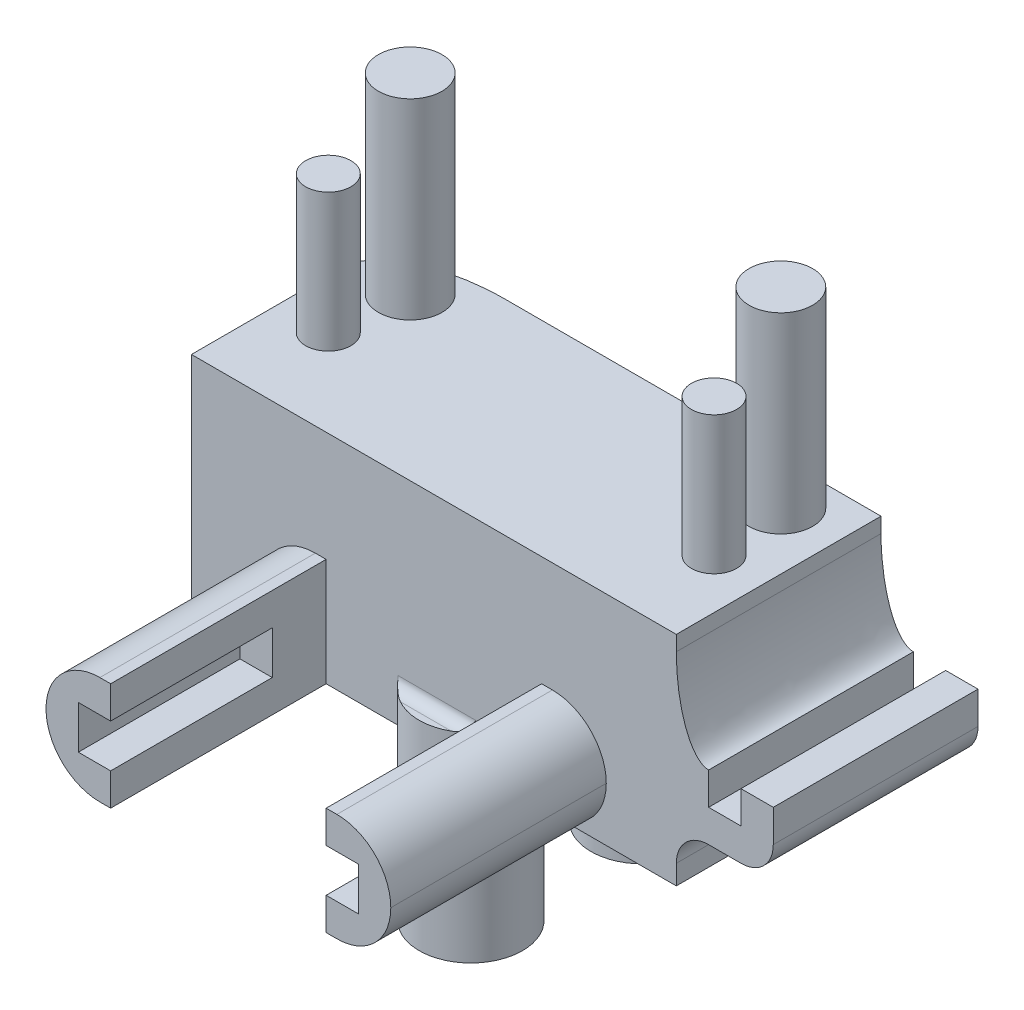
SolidWorks part; units mm, degrees
ref_plane "Front Plane" through (0, 0, 0) normal (0, 0, 1) x (1, 0, 0)
ref_plane "Top Plane" through (0, 0, 0) normal (0, 1, 0) x (1, 0, 0)
ref_plane "Right Plane" through (0, 0, 0) normal (1, 0, 0) x (0, 0, -1)
sketch "Sketch1" plane through (0, 0, 0) normal (0, 1, 0) x (1, 0, 0)
  line L1 (-40.1858, -24.5795) -> (-17.6858, -24.5795)
  line L2 (-40.1858, -24.5795) -> (-40.1858, -17.5795)
  line L3 (-40.1858, -17.5795) -> (-17.6858, -17.5795)
  line L4 (-17.6858, -24.5795) -> (-17.6858, -17.5795)
  dimension "D1" = 22.5
  dimension "D2" = 7
extrude "Boss-Extrude1" add sketch "Sketch1" along normal blind 1.5
sketch "Sketch2" plane through (0, 1.5, 0) normal (0, 1, 0) x (1, 0, 0)
  line L0 (-17.6858, -24.5795) -> (-17.6858, -17.5795) construction
  line L2 (-40.1858, -24.5795) -> (-17.6858, -24.5795) construction
  circle A0 centre (-37.5358, -19.5795) radius 1.475
  circle A1 centre (-20.3358, -19.5795) radius 1.475
  dimension "D1" = 2.95
  dimension "D2" = 2.95
  dimension "D3" = 17.2
  dimension "D4" = 2.65
  dimension "D5" = 5
  dimension "D6" = 5
extrude "Boss-Extrude2" add sketch "Sketch2" along normal blind 11.5
sketch "Sketch3" plane through (0, 1.5, 0) normal (0, 1, 0) x (1, 0, 0)
  circle A0 centre (-37.8858, -23.0295) radius 1.05
  circle A1 centre (-19.9858, -23.0295) radius 1.05
  circle A2 centre (-37.5358, -19.5795) radius 1.475 construction
  circle A3 centre (-20.3358, -19.5795) radius 1.475 construction
  dimension "D1" = 2.1
  dimension "D2" = 2.1
  dimension "D3" = 0.35
  dimension "D4" = 0.35
  dimension "D5" = 3.45
  dimension "D6" = 3.45
extrude "Boss-Extrude3" add sketch "Sketch3" along normal blind 9
sketch "Sketch4" plane through (0, 0, 0) normal (0, -1, 0) x (-1, 0, 0)
  line L0 (40.1858, -17.5795) -> (40.1858, -24.5795) construction
  line L1 (17.6858, -24.5795) -> (40.1858, -24.5795)
  line L2 (17.6858, -24.5795) -> (17.6858, -27.0795)
  line L3 (17.6858, -27.0795) -> (40.1858, -27.0795)
  line L4 (40.1858, -24.5795) -> (40.1858, -27.0795)
  line L6 (20.9358, -27.0795) -> (23.9358, -27.0795)
  line L7 (20.9358, -27.0795) -> (20.9358, -29.9823)
  line L8 (20.9358, -29.9823) -> (23.9358, -29.9823)
  line L9 (23.9358, -27.0795) -> (23.9358, -29.9823)
  line L10 (32.4358, -27.0795) -> (35.4358, -27.0795)
  line L11 (32.4358, -27.0795) -> (32.4358, -28.8632)
  line L12 (32.4358, -28.8632) -> (35.4358, -28.8632)
  line L13 (35.4358, -27.0795) -> (35.4358, -28.8632)
  line M13 (40.1858, -24.5795) -> (40.1858, -17.5795)
  line M14 (40.1858, -17.5795) -> (17.6858, -17.5795)
  line M15 (17.6858, -17.5795) -> (17.6858, -24.5795)
  line M16 (17.6858, -24.5795) -> (40.1858, -24.5795)
  dimension "D1" = 0
  dimension "D2" = 3.25
  dimension "D3" = 4.75
  dimension "D4" = 2.5
  dimension "D5" = 3
  dimension "D6" = 3
extrude "Boss-Extrude4" add sketch "Sketch4" along normal blind 6 and the other way blind 1.5 contours L4 L2 L3 M16 | M16 M13 M14 M15
sketch "Sketch8" plane through (0, 1.5, 0) normal (0, 1, 0) x (1, 0, 0)
  line L1 (-40.1858, -17.5795) -> (-17.6858, -17.5795)
  line L2 (-40.1858, -17.5795) -> (-40.1858, -27.0795)
  line L3 (-40.1858, -27.0795) -> (-17.6858, -27.0795)
  line L4 (-17.6858, -17.5795) -> (-17.6858, -27.0795)
extrude "Boss-Extrude7" add sketch "Sketch8" along normal blind 2.61
sketch "Sketch9" plane through (0, -6, 0) normal (0, -1, 0) x (-1, 0, 0)
  line L0 (17.6858, -17.5795) -> (17.6858, -27.0795) construction
  line L3 (17.6858, -27.0795) -> (40.1858, -27.0795) construction
  circle A0 centre (28.8108, -25.4895) radius 2.4
  circle A1 centre (28.8108, -17.5195) radius 2.4
  dimension "D1" = 11.125
  dimension "D2" = 11.125
  dimension "D3" = 4.8
  dimension "D4" = 4.8
  dimension "D5" = 1.59
  dimension "D6" = 7.97
extrude "Boss-Extrude8" add sketch "Sketch9" along normal blind 7.76 and the other way blind 1.5
sketch "Sketch11" plane through (-17.6858, 0, 0) normal (1, 0, 0) x (0, 0, -1)
  line L0 (-27.0795, 4.11) -> (-17.5795, 4.11) construction
  line L1 (-17.5795, -0.59) -> (-27.0795, -0.59)
  line L2 (-17.5795, -0.59) -> (-17.5795, -3.59)
  line L3 (-17.5795, -3.59) -> (-27.0795, -3.59)
  line L4 (-27.0795, -0.59) -> (-27.0795, -3.59)
  line L5 (-17.5795, 4.11) -> (-17.5795, -6) construction
  line L6 (-27.0795, 4.11) -> (-27.0795, -6) construction
  point P8 (-17.5795, -0.945)
  dimension "D1" = 4.7
  dimension "D2" = 0
  dimension "D3" = 0
  dimension "D4" = 3
extrude "Boss-Extrude9" add sketch "Sketch11" along normal blind 4.5
sketch "Sketch16" plane through (0, -0.59, 0) normal (0, 1, 0) x (1, 0, 0)
  line L0 (-13.1858, -27.0795) -> (-17.6858, -27.0795) construction
  line L1 (-14.6858, -27.0795) -> (-16.1858, -27.0795)
  line L2 (-14.6858, -27.0795) -> (-14.6858, -17.5795)
  line L3 (-14.6858, -17.5795) -> (-16.1858, -17.5795)
  line L4 (-16.1858, -27.0795) -> (-16.1858, -17.5795)
  line L5 (-13.1858, -17.5795) -> (-17.6858, -17.5795) construction
  line L6 (-13.1858, -17.5795) -> (-13.1858, -27.0795) construction
  line L7 (-17.6858, -17.5795) -> (-17.6858, -27.0795) construction
  dimension "D1" = 1.5
  dimension "D2" = 1.5
extrude "Cut-Extrude2" cut sketch "Sketch16" against normal blind 1.5
sketch "Sketch19" plane through (0, 0, 27.0795) normal (0, 0, 1) x (1, 0, 0)
  line L0 (-17.6858, -6) -> (-27.013, -6) construction
  line L1 (-20.9358, -6) -> (-23.9358, -6)
  line L2 (-20.9358, -6) -> (-20.9358, -1)
  line L3 (-20.9358, -1) -> (-23.9358, -1)
  line L4 (-23.9358, -6) -> (-23.9358, -1)
  line L5 (-30.6085, -6) -> (-40.1858, -6) construction
  line L6 (-36.9358, -6) -> (-33.9358, -6)
  line L7 (-36.9358, -6) -> (-36.9358, -1)
  line L8 (-36.9358, -1) -> (-33.9358, -1)
  line L9 (-33.9358, -6) -> (-33.9358, -1)
  line L10 (-17.6858, -3.59) -> (-17.6858, -6) construction
  line L11 (-40.1858, 4.11) -> (-40.1858, -6) construction
  point P12 (-30.3422, -6.6855)
  dimension "D1" = 3.25
  dimension "D2" = 5
  dimension "D3" = 5
  dimension "D4" = 3.25
  dimension "D5" = 3
  dimension "D6" = 3
extrude "Boss-Extrude10" add sketch "Sketch19" along normal blind 10
sketch "Sketch20" plane through (0, 0, 37.0795) normal (0, 0, 1) x (1, 0, 0)
  line L0 (-20.9358, -6) -> (-20.9358, -1) construction
  line L1 (-22.4358, -4.5) -> (-35.4358, -4.5)
  line L2 (-22.4358, -4.5) -> (-22.4358, -2.5)
  line L3 (-22.4358, -2.5) -> (-35.4358, -2.5)
  line L4 (-35.4358, -4.5) -> (-35.4358, -2.5)
  line L5 (-23.9358, -6) -> (-20.9358, -6) construction
  line L6 (-33.9358, -1) -> (-36.9358, -1) construction
  line L7 (-36.9358, -1) -> (-36.9358, -6) construction
  point P4 (-33.3237, -3.0588)
  dimension "D1" = 1.5
  dimension "D2" = 1.5
  dimension "D3" = 1.5
  dimension "D4" = 1.5
extrude "Cut-Extrude3" cut sketch "Sketch20" against normal blind 7.5
fillet "Fillet1" radius 1.5 3 edges at (-16.9358, -0.59, 27.0795) (-16.9358, -0.59, 17.5795) (-17.6858, -0.59, 22.3295)
fillet "Fillet2" radius 1.5 1 edges at (-17.6858, -3.59, 22.3295)
fillet "Fillet3" radius 1.5 1 edges at (-13.1858, -3.59, 22.3295)
fillet "Fillet4" radius 2 1 edges at (-28.8108, -4.5, 17.5795)
fillet "Fillet5" radius 0.5 1 edges at (-28.8108, -4.5, 27.0795)
fillet "Fillet6" radius 2.5 4 edges at (-40.1858, -6, 22.3295) (-35.6979, -6, 17.5795) (-40.1858, 4.11, 22.3295) (-40.1858, -0.945, 17.5795)
fillet "Fillet7" radius 2.5 1 edges at (-36.9358, -6, 32.0795)
fillet "Fillet8" radius 2.5 3 edges at (-36.9358, -2.25, 27.0795) (-36.9358, -1, 32.0795) (-36.9358, -2.25, 37.0795)
fillet "Fillet9" radius 2.5 1 edges at (-20.9358, -1, 32.0795)
fillet "Fillet10" radius 2.5 3 edges at (-20.9358, -4.75, 27.0795) (-20.9358, -6, 32.0795) (-20.9358, -4.75, 37.0795)
